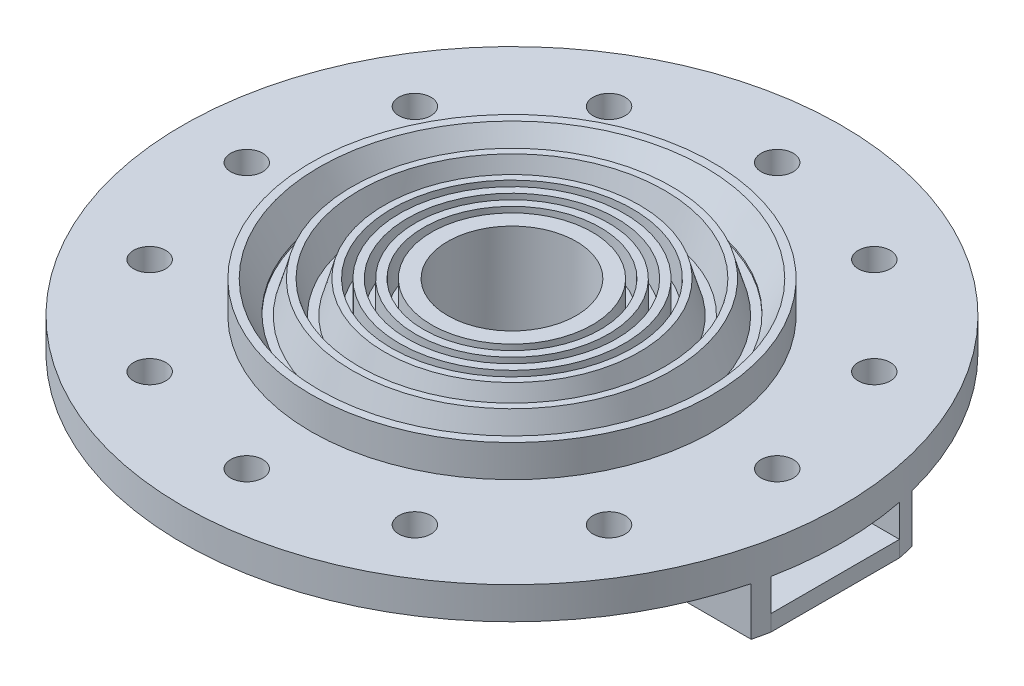
SolidWorks part; units mm, degrees
ref_plane "Front Plane" through (0, 0, 0) normal (0, 0, 1) x (1, 0, 0)
ref_plane "Top Plane" through (0, 0, 0) normal (0, 1, 0) x (1, 0, 0)
ref_plane "Right Plane" through (0, 0, 0) normal (1, 0, 0) x (0, 0, -1)
sketch "Sketch1" plane through (0, 0, 0) normal (0, 1, 0) x (1, 0, 0)
  line L0 (0, 15.875) -> (63.1218, 15.875)
  line L1 (0, 15.875) -> (0, 12.7)
  line L2 (0, -15.875) -> (0, -12.7)
  line L3 (0, 12.7) -> (63.8365, 12.7)
  line L4 (0, -12.7) -> (63.8365, -12.7)
  line L13 (0, -15.875) -> (63.1218, -15.875)
  circle A0 centre (0, 0) radius 39.6875
  circle A1 centre (0, 0) radius 30.1625
  circle A2 centre (0, 0) radius 31.75
  circle A3 centre (0, 0) radius 36.5125
  circle A4 centre (0, 0) radius 25.4
  circle A5 centre (0, 0) radius 23.8125
  circle A6 centre (0, 0) radius 15.875
  circle A7 centre (0, 0) radius 12.7
  circle A8 centre (0, 0) radius 65.0875
  circle A9 centre (0, 0) radius 22.225
  circle A10 centre (-26.1938, 45.3689) radius 3.175
  circle A11 centre (0, 52.3875) radius 3.175
  circle A12 centre (26.1937, 45.3689) radius 3.175
  circle A13 centre (45.3689, 26.1938) radius 3.175
  circle A14 centre (52.3875, 0) radius 3.175
  circle A15 centre (-45.3689, 26.1937) radius 3.175
  circle A16 centre (0, 0) radius 33.3375
  circle A17 centre (0, 0) radius 34.925
  circle A18 centre (0, 0) radius 28.575
  circle A19 centre (0, 0) radius 26.9875
  circle A20 centre (-52.3875, 0) radius 3.175
  circle A21 centre (-45.3689, -26.1938) radius 3.175
  circle A22 centre (-26.1937, -45.3689) radius 3.175
  circle A23 centre (0, -52.3875) radius 3.175
  circle A24 centre (26.1938, -45.3689) radius 3.175
  circle A25 centre (45.3689, -26.1937) radius 3.175
  circle A26 centre (0, 0) radius 20.6375
  circle A27 centre (0, 0) radius 19.05
  circle A28 centre (0, 0) radius 17.4625
extrude "Boss-Extrude2" add sketch "Sketch1" along normal blind 12.7 contours A3 L0 A0 L13 | A17 L0 A3 L13 | L0 A16 L13 A2 | L0 A2 L13 A1 | A18 L0 A1 L13 | L0 A19 L13 A4 | A5 L0 A4 L13 | A7 L1 A6 L2 | L3 A6 L1 | A7 L4 A6 L3 | L2 A6 L4 | A5 L13 A4 L4 | L13 A19 L4 A4 | A18 L13 A1 L4 | L13 A2 L4 A1 | L13 A16 L4 A2 | A17 L13 A3 L4 | A3 L13 A0 L4 | A3 L4 A0 L3 | A17 L4 A3 L3 | L4 A16 L3 A2 | L4 A2 L3 A1 | A18 L4 A1 L3 | L4 A19 L3 A4 | A5 L4 A4 L3 | A5 L3 A4 L0 | L3 A19 L0 A4 | A18 L3 A1 L0 | L3 A2 L0 A1 | L3 A16 L0 A2 | A17 L3 A3 L0 | A3 L3 A0 L0 region at (3.6248, 0, -13.9816) region at (-0.355, 0, -14.2875) region at (4.7625, 0, -12.4005) region at (3.6248, 0, 13.9816) region at (-24.4927, 0, 0) region at (19.9716, 0, -14.3177) region at (-26.1277, 0, 0) region at (21.904, 0, -14.3126) region at (21.0701, 0, -12.4406) region at (19.9716, 0, 14.3177) region at (22.9048, 0, -12.4411) region at (21.904, 0, 14.3126) region at (-29.3968, 0, 0) region at (25.6235, 0, -14.3058) region at (-31.031, 0, 0) region at (27.4309, 0, -14.3035) region at (26.4781, 0, -12.4419) region at (25.6235, 0, 14.3058) region at (-32.6649, 0, 0) region at (29.2124, 0, -14.3016) region at (28.2289, 0, -12.4422) region at (27.4309, 0, 14.3035) region at (29.9615, 0, -12.4425) region at (29.2124, 0, 14.3016) region at (-35.9324, 0, 0) region at (32.7147, 0, -14.2987) region at (-37.6119, 0, 0) region at (35.296, 0, -14.2972) region at (34.9369, 0, 0) region at (32.7147, 0, 14.2987) region at (37.3695, 0, 0) region at (35.296, 0, 14.2972)
chamfer "Chamfer1" distance 3.175 angle 62 1 edges at (0, 12.7, 34.925) first distance on face at (0, 12.7, 39.6875)
chamfer "Chamfer2" distance 6.35 angle 16 1 edges at (0, 12.7, 33.3375) first distance on face at (0, 12.7, 33.3375)
chamfer "Chamfer3" distance 1.5875 angle 76 1 edges at (0, 12.7, 28.575) first distance on face at (0, 12.7, 31.5167)
chamfer "Chamfer4" distance 6.35 angle 16 1 edges at (0, 12.7, 26.9875) first distance on face at (0, 12.7, 26.9875)
extrude "Boss-Extrude3" add sketch "Sketch1<20>" along normal blind 6.35 contours L0 A8 L13 A0 A25 A24 A23 A22 A21 A20 A15 A13 A12 A11 A10 | L13 A8 L4 A0 | L4 A8 L3 A0 A14 | L3 A8 L0 A0 | L0 A17 L13 A16 | A19 L0 A18 L13 | L13 A17 L4 A16 | L4 A17 L3 A16 | L3 A17 L0 A16 | A19 L3 A18 L0 | A19 L4 A18 L3 | A19 L13 A18 L4 | A9 L13 A5 L4 | A27 L13 A26 L4 | L13 A28 L4 A6 | L4 A28 L3 A6 | A27 L4 A26 L3 | A9 L4 A5 L3 | A9 L0 A5 L13 | A27 L0 A26 L13 | L0 A28 L13 A6 | A9 L3 A5 L0 | A27 L3 A26 L0 | L3 A28 L0 A6 region at (-16.303, 0, 0) region at (7.7398, 0, -14.5099) region at (7.7398, 0, 14.5099) region at (10.7552, 0, -12.4339) region at (-19.5836, 0, 0) region at (13.6102, 0, -14.3531) region at (15.233, 0, -12.438) region at (13.6102, 0, 14.3531) region at (-22.8571, 0, 0) region at (17.9686, 0, -14.3249) region at (19.1911, 0, -12.44) region at (17.9686, 0, 14.3249) region at (-27.7624, 0, 0) region at (23.784, 0, -14.3088) region at (24.7051, 0, -12.4416) region at (23.784, 0, 14.3088) region at (-34.2987, 0, 0) region at (30.9725, 0, -14.3) region at (31.6789, 0, -12.4427) region at (30.9725, 0, 14.3) region at (-41.5146, 0, 0) region at (50.2517, 0, -14.2926) region at (50.7185, 0, -12.3257) region at (50.2517, 0, 14.2926)
sketch "Sketch1<20>" plane through (0, 0, 0) normal (0, 1, 0) x (1, 0, 0) same geometry as "Sketch1"
extrude "Boss-Extrude4" add sketch "Sketch1<21>" along normal blind 12.7 contours A28 L4 A27 L3 | A26 L4 A9 L3 | A26 L13 A9 L4 | A28 L13 A27 L4 | A26 L0 A9 L13 | A28 L0 A27 L13 | A28 L3 A27 L0 | A26 L3 A9 L0 region at (-17.9448, 0, 0) region at (11.0831, 0, -14.3875) region at (13.0922, 0, -12.4364) region at (11.0831, 0, 14.3875) region at (-21.2209, 0, 0) region at (15.8658, 0, -14.3356) region at (17.253, 0, -12.4391) region at (15.8658, 0, 14.3356)
sketch "Sketch1<21>" plane through (0, 0, 0) normal (0, 1, 0) x (1, 0, 0) same geometry as "Sketch1"
extrude "Boss-Extrude6" add sketch "Sketch1<24>" against normal blind 6.35 contours L3 A8 L0 A0 | A3 L3 A0 L0 | A17 L3 A3 L0 | L3 A17 L0 A16 | L3 A16 L0 A2 | L3 A2 L0 A1 | A18 L3 A1 L0 | A19 L3 A18 L0 | L3 A19 L0 A4 | A5 L3 A4 L0 | A9 L3 A5 L0 | A26 L3 A9 L0 | A27 L3 A26 L0 | A28 L3 A27 L0 | L3 A28 L0 A6 | L3 A6 L1 | A7 L1 A6 L2 | L2 A6 L4 | L13 A28 L4 A6 | A28 L13 A27 L4 | A27 L13 A26 L4 | A26 L13 A9 L4 | A9 L13 A5 L4 | A5 L13 A4 L4 | L13 A19 L4 A4 | A19 L13 A18 L4 | A18 L13 A1 L4 | L13 A2 L4 A1 | L13 A16 L4 A2 | L13 A17 L4 A16 | A17 L13 A3 L4 | A3 L13 A0 L4 | L13 A8 L4 A0 region at (3.6248, 0, -13.9816) region at (-0.355, 0, -14.2875) region at (7.7398, 0, -14.5099) region at (11.0831, 0, -14.3875) region at (7.7398, 0, 14.5099) region at (3.6248, 0, 13.9816) region at (13.6102, 0, -14.3531) region at (11.0831, 0, 14.3875) region at (15.8658, 0, -14.3356) region at (13.6102, 0, 14.3531) region at (17.9686, 0, -14.3249) region at (15.8658, 0, 14.3356) region at (19.9716, 0, -14.3177) region at (17.9686, 0, 14.3249) region at (21.904, 0, -14.3126) region at (19.9716, 0, 14.3177) region at (23.784, 0, -14.3088) region at (21.904, 0, 14.3126) region at (25.6235, 0, -14.3058) region at (23.784, 0, 14.3088) region at (27.4309, 0, -14.3035) region at (25.6235, 0, 14.3058) region at (29.2124, 0, -14.3016) region at (27.4309, 0, 14.3035) region at (30.9725, 0, -14.3) region at (29.2124, 0, 14.3016) region at (32.7147, 0, -14.2987) region at (30.9725, 0, 14.3) region at (35.296, 0, -14.2972) region at (32.7147, 0, 14.2987) region at (50.2517, 0, -14.2926) region at (35.296, 0, 14.2972) region at (50.2517, 0, 14.2926)
sketch "Sketch1<24>" plane through (0, 0, 0) normal (0, 1, 0) x (1, 0, 0) same geometry as "Sketch1"
sketch "Sketch2" plane through (0, -6.35, 0) normal (0, -1, 0) x (-1, 0, 0)
  line L0 (0, 12.7) -> (-63.8365, 12.7)
  line L1 (0, 15.875) -> (-63.1218, 15.875)
  line L2 (0, -12.7) -> (-63.8365, -12.7)
  line L3 (0, -15.875) -> (-63.5, -15.875)
  line L4 (0, -15.875) -> (-63.1218, -15.875) construction
  line L6 (-63.1218, 15.875) -> (0, 15.875)
  line L7 (-63.1218, 15.875) -> (-63.1218, -15.875)
  line L8 (-63.1218, -15.875) -> (0, -15.875)
  line L9 (0, 15.875) -> (0, -15.875)
  line L10 (-63.8365, 12.7) -> (0, 12.7)
  line L11 (-63.8365, 12.7) -> (-63.8365, -12.7)
  line L12 (-63.8365, -12.7) -> (0, -12.7)
  line L13 (0, 12.7) -> (0, -12.7)
  circle A0 centre (0, 0) radius 12.7
  circle A1 centre (0, 0) radius 15.875
  line M5 (-63.8365, 12.7) -> (0, 12.7)
  arc M6 (0, 12.7) -> (0, -12.7) centre (0, 0) cw
  line M7 (0, -12.7) -> (-63.8365, -12.7)
  arc M8 (-63.8365, -12.7) -> (-63.1218, -15.875) centre (0, 0) ccw
  line M9 (-63.1218, -15.875) -> (0, -15.875)
  arc M10 (0, -15.875) -> (0, 15.875) centre (0, 0) ccw
  line M11 (0, 15.875) -> (-63.1218, 15.875)
  arc M12 (-63.1218, 15.875) -> (-63.8365, 12.7) centre (0, 0) ccw
extrude "Boss-Extrude7" add sketch "Sketch2" along normal blind 3.175 contours A1 L0 L7 L12 | L11 L2 L7 M5 | L7 M12 M5 | L7 L2 M8 | A1 L12 L7 M9 | A1 L7 L0 M11 | L9 M10 M6 | L10 A1 A0 M7 | L9 A1 L10 | A1 L9 M7 | L9 M6 | L9 A0 region at (12.9995, -6.35, 0) region at (3.6248, -6.35, -13.9816) region at (-5.39, -6.35, 0) region at (-0.355, -6.35, -14.2875) region at (5.39, -6.35, 0) region at (38.509, -6.35, 0) region at (34.7618, -6.35, -14.3226) region at (3.6248, -6.35, 13.9816) region at (63.4791, -6.35, 0) region at (63.3648, -6.35, -13.7782) region at (34.7618, -6.35, 14.3226) region at (63.3648, -6.35, 13.7782)
